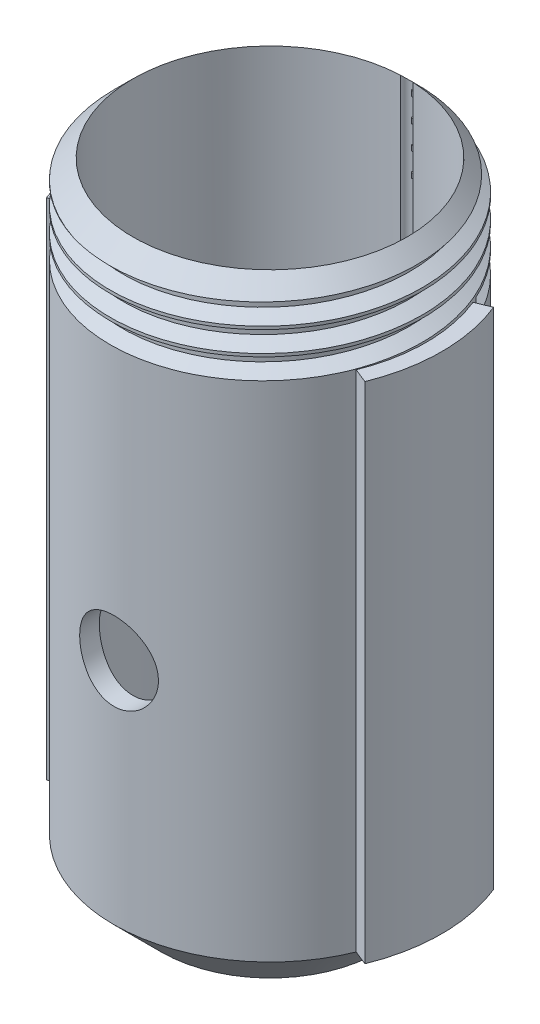
SolidWorks part; units mm, degrees
ref_plane "Alzado" through (0, 0, 0) normal (0, 0, 1) x (1, 0, 0)
ref_plane "Planta" through (0, 0, 0) normal (0, 1, 0) x (1, 0, 0)
ref_plane "Vista lateral" through (0, 0, 0) normal (1, 0, 0) x (0, 0, -1)
sketch "Croquis1" plane through (0, 0, 0) normal (0, 0, 1) x (1, 0, 0)
  line L0 (0, 0) -> (0, 3) construction
  line L1 (0, 0) -> (0, 54.3825) construction
  line L2 (0, 0) -> (-9.9, 0)
  line L3 (0, 0) -> (0, 3)
  line L4 (-8.7, 40.5) -> (-9.9, 40.5)
  line L5 (-9.9, 0) -> (-9.9, 40.5)
  line L8 (0, 3) -> (-8.7, 3)
  line L9 (-8.7, 40.5) -> (-8.7, 3)
  dimension "D1" = 9.9
  dimension "D2" = 40.5
  dimension "D3" = 1.2
  dimension "D4" = 3
revolve "Revolución1" add sketch "Croquis1" angle 360 about L1
chamfer "Chaflán1" distance 1.5 angle 45 1 edges at (0, 40.5, -9.9)
chamfer "Chaflán2" distance 3 angle 45 1 edges at (0, 0, -9.9)
sketch "Croquis2" plane through (0, 0, 0) normal (0, 0, 1) x (1, 0, 0)
  line L0 (8.7, 3) -> (-8.7, 3) construction
  circle A0 centre (0, 7.5) radius 0.5
  circle A1 centre (0, 27.5) radius 0.5
  circle A2 centre (0, 5) radius 1.25
  circle A3 centre (0, 12) radius 2.75
  dimension "D1" = 1
  dimension "D2" = 4.5
  dimension "D3" = 20
  dimension "D4" = 2.5
  dimension "D6" = 5.5
  dimension "D5" = 2.5
  dimension "D7" = 4.5
extrude "Cortar-Extruir3" cut sketch "Croquis2" against normal up to next
ref_plane "Plano1" through (0, 27.5, 0) normal (0, -1, 0) x (-1, 0, 0)
sketch "Croquis5" plane through (0, 27.5, 0) normal (0, -1, 0) x (-1, 0, 0)
  circle A0 centre (0, 0) radius 7
sketch "Croquis7" plane through (0, 0, 0) normal (0, 0, 1) x (1, 0, 0)
  line L0 (-6.9, 0) -> (6.9, 0) construction
  circle A0 centre (0, 17.5) radius 2.5
  dimension "D1" = 5
  dimension "D2" = 17.5
extrude "Cortar-Extruir4" cut sketch "Croquis7" along normal up to next
thread "Rosca1" pitch 1.5 method cut profile "Perfil de rosca1" start angle 0, offset 0, length 5.15, pitch 1.5, diameter 19.8
ref_plane "Plano2" through (-9.9, 40.2, 0) normal (0, 0, 1) x (-1, 0, 0)
sketch "Perfil de rosca1" plane through (-9.9, 40.2, 0) normal (0, 0, 1) x (-1, 0, 0)
  line L0 (0, 0) -> (0, 1.5) construction
  line L11 (0, 0) -> (0, 1.3125)
  line L12 (0, 1.3125) -> (-0.8119, 0.8437)
  line L13 (-0.8119, 0.8437) -> (-0.8119, 0.4687)
  line L15 (-0.8119, 0.4687) -> (0, 0)
  line L17 (-0.8119, 0.6562) -> (0, 0.6562) construction
  point P2 (0, 0)
  dimension "Pitch" = 1.5
  dimension "Profile_Angle" = 60
  dimension "Profile_Land" = 0.375
  dimension "Profile_Height" = 0.8119
fillet "Redondeo3" radius 1 2 edges at (-0.4868, 27.3859, -8.6864) (-0.4868, 7.3859, -8.6864)
sketch "Croquis8" plane through (0, 0, 0) normal (0, -1, 0) x (1, 0, 0)
  line L1 (1.5588, 0) -> (0.7794, 1.35)
  line L2 (0.7794, 1.35) -> (-0.7794, 1.35)
  line L3 (-0.7794, 1.35) -> (-1.5588, 0)
  line L4 (-1.5588, 0) -> (-0.7794, -1.35)
  line L5 (-0.7794, -1.35) -> (0.7794, -1.35)
  line L6 (0.7794, -1.35) -> (1.5588, 0)
  circle A0 centre (0, 0) radius 1.35 construction
  dimension "D1" = 2.7
extrude "Cortar-Extruir5" cut sketch "Croquis8" against normal blind 2
ref_plane "Plano4" through (0, 40.2, 0) normal (0, -1, 0) x (-1, 0, 0)
sketch "Croquis9" plane through (0, 40.2, 0) normal (0, 1, 0) x (1, 0, 0)
  circle A0 centre (0, 8.7) radius 0.4
  circle A3 centre (0, 0) radius 8.7 construction
  point P2 (0, 0)
  point P3 (0, 8.7)
  point P6 (0, 0)
  point P7 (0, 8)
  dimension "0.7" = 0.8
extrude "Cortar-Extruir6" cut sketch "Croquis9" against normal blind 33
ref_plane "Plano3" through (0, 3, 0) normal (0, -1, 0) x (-1, 0, 0)
sketch "Croquis10" plane through (0, 3, 0) normal (0, -1, 0) x (-1, 0, 0)
  line L0 (-15.5643, 0) -> (14.7161, 0) construction
  line L1 (0, 0) -> (-10.1063, 4.0832)
  line L2 (0, 0) -> (-10.1063, -4.0832)
  line L3 (0, 0) -> (10.1063, 4.0832)
  line L4 (0, 0) -> (10.1063, -4.0832)
  arc A0 (-10.1063, 4.0832) -> (-10.1063, -4.0832) centre (0, 0) ccw
  arc A1 (10.1063, 4.0832) -> (10.1063, -4.0832) centre (0, 0) cw
  circle A2 centre (0, 0) radius 9.9
  dimension "D3" = 10.9
  dimension "D4" = 19.8
  dimension "D1" = 44
  dimension "D2" = 22
extrude "Saliente-Extruir1" add sketch "Croquis10" against normal blind 32 contours A0 L0 A2 L1 | L0 A0 L2 A2 | A2 L0 A1 L3 | L0 A2 L4 A1
sketch "Croquis11" plane through (0, 2, 0) normal (0, -1, 0) x (-1, 0, 0)
  circle A0 centre (0, 0) radius 0.75
  dimension "D1" = 1.5
extrude "Cortar-Extruir8" cut sketch "Croquis11" against normal offset from surface (0.8 mm away) 0.2 up to face at (0, 3, -8.7)
